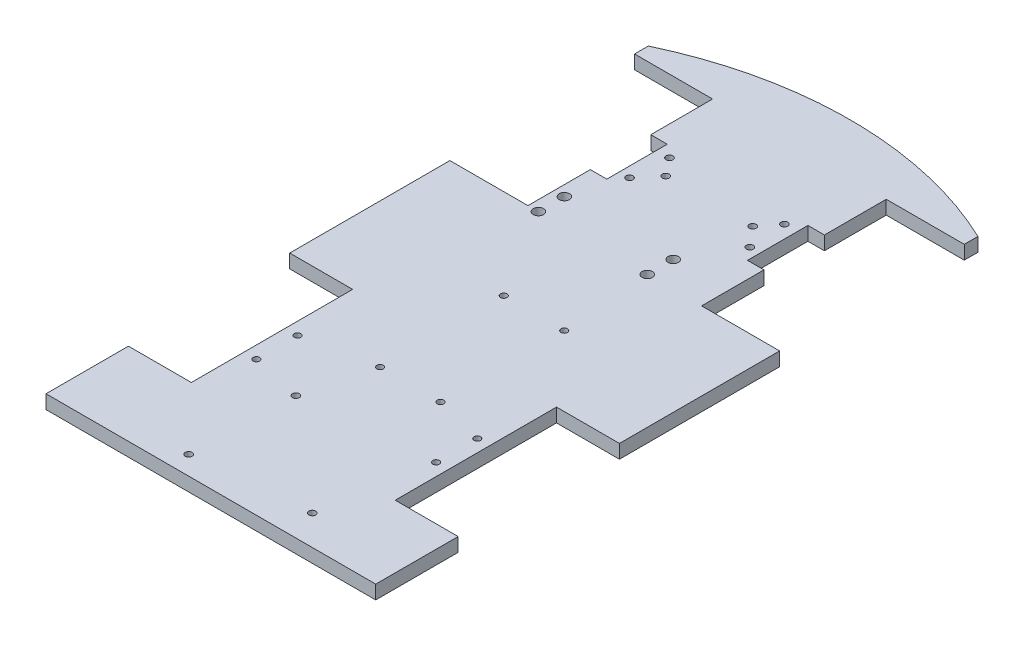
SolidWorks part; units mm, degrees
material "Oak"
ref_plane "Front Plane" through (0, 0, 0) normal (0, 0, 1) x (1, 0, 0)
ref_plane "Top Plane" through (0, 0, 0) normal (0, 1, 0) x (1, 0, 0)
ref_plane "Right Plane" through (0, 0, 0) normal (1, 0, 0) x (0, 0, -1)
sketch "Sketch1" plane through (0, 0, 0) normal (0, 1, 0) x (1, 0, 0)
  line L0 (50.292, 32.512) -> (76.2, 32.512) construction
  line L1 (0, 0) -> (0, -280.955) construction
  line L2 (0, 66.1738) -> (0, -229.362)
  line L3 (76.2, -229.362) -> (0, -229.362)
  line L7 (50.292, 32.512) -> (50.292, -32.512) construction
  line L8 (50.292, -32.512) -> (76.2, -32.512) construction
  line L9 (76.2, 32.512) -> (76.2, -32.512) construction
  line L10 (50.292, 32.512) -> (76.2, -32.512) construction
  line L11 (50.292, -32.512) -> (76.2, 32.512) construction
  line L18 (50.292, -119.888) -> (76.2, -119.888) construction
  line L19 (50.292, -119.888) -> (50.292, -184.912) construction
  line L20 (50.292, -184.912) -> (76.2, -184.912) construction
  line L21 (76.2, -119.888) -> (76.2, -184.912) construction
  line L22 (50.292, -119.888) -> (76.2, -184.912) construction
  line L23 (50.292, -184.912) -> (76.2, -119.888) construction
  line L25 (-76.2, 0) -> (76.2, 0) construction
  line L27 (-76.2, -152.4) -> (76.2, -152.4) construction
  line L28 (76.2, 0) -> (76.2, -152.4) construction
  line L33 (40.132, -42.672) -> (76.2, -42.672)
  line L34 (40.132, 42.672) -> (40.132, 14.097)
  line L35 (40.132, 42.672) -> (76.2, 42.672)
  line L36 (47.117, -191.262) -> (76.2, -191.262)
  line L37 (47.117, -116.713) -> (47.117, -191.262)
  line L38 (47.117, -116.713) -> (76.2, -116.713)
  line L43 (76.2, -42.672) -> (76.2, -116.713)
  line L45 (76.2, 42.672) -> (76.2, 49.022)
  line L47 (76.2, -191.262) -> (76.2, -229.362)
  line L55 (32.512, -13.843) -> (40.132, -13.843)
  line L56 (32.512, 14.097) -> (32.512, -13.843)
  line L57 (32.512, 14.097) -> (40.132, 14.097)
  line L58 (40.132, -13.843) -> (40.132, -42.672)
  arc A0 (0, 66.1738) -> (76.2, 49.022) centre (0, -111.6688) cw
  point P9 (63.246, 0)
  point P19 (63.246, -152.4)
  dimension "D7" = 3.175
  dimension "D8" = 6.35
  dimension "D12" = 7.62
  dimension "D16" = 6.35
  dimension "D1" = 152.4
  dimension "D2" = 152.4
  dimension "D3" = 126.492
  dimension "D4" = 25.908
  dimension "D6" = 3.175
  dimension "D9" = 10.16
  dimension "D10" = 10.16
  dimension "D5" = 65.024
  dimension "D11" = 10.16
  dimension "D13" = 27.94
  dimension "D14" = 28.575
  dimension "D15" = 38.1
extrude "Chassis" add sketch "Sketch1" along normal blind 6.35 contours L47 L36 L37 L38 L43 L33 L34 L55 L56 L57 L35 L45 region at (30.845, 0, 91.965)
mirror "Mirror1" about plane through (0, 6.35, 0) normal (1, 0, 0) of "Chassis"
sketch "Sketch2" plane through (0, 0, 0) normal (0, 1, 0) x (1, 0, 0)
  circle A0 centre (-26.5557, 9.17) radius 1.5875 construction
  circle A1 centre (-17.7031, -172.3599) radius 1.5875
  circle A2 centre (-17.7031, -172.3599) radius 1.5875
  circle A3 centre (-18.9731, -220.6199) radius 1.5875
  circle A4 centre (-18.9731, -220.6199) radius 1.5875
  circle A5 centre (33.0969, -215.5399) radius 1.5875
  circle A6 centre (33.0969, -215.5399) radius 1.5875
  circle A7 centre (-20.1056, 0.9994) radius 1.5875 construction
  circle A8 centre (-27.7865, -8.0406) radius 1.5875 construction
  circle A9 centre (26.5557, 9.17) radius 1.5875 construction
  circle A10 centre (20.1056, 0.9994) radius 1.5875 construction
  circle A11 centre (27.7865, -8.0406) radius 1.5875 construction
  circle A12 centre (15, -30.6528) radius 2.3812 construction
  circle A13 centre (15, -42.6528) radius 2.3813 construction
  circle A14 centre (-35.3, -30.6528) radius 2.3813 construction
  circle A15 centre (-35.3, -42.6528) radius 2.3813 construction
  circle A16 centre (18.288, -84.328) radius 1.5 construction
  circle A17 centre (-9.652, -84.328) radius 1.5 construction
  circle A18 centre (18.288, -141.478) radius 1.5 construction
  circle A19 centre (-9.652, -141.478) radius 1.5 construction
  circle A20 centre (-41.402, -147.875) radius 1.5 construction
  circle A21 centre (-41.402, -166.925) radius 1.5 construction
  circle A22 centre (41.402, -147.6053) radius 1.5 construction
  circle A23 centre (41.402, -166.6553) radius 1.5 construction
  circle A24 centre (-26.5557, 9.17) radius 1.5875
  circle A25 centre (-20.1056, 0.9994) radius 1.5875
  circle A26 centre (-27.7865, -8.0406) radius 1.5875
  circle A27 centre (26.5557, 9.17) radius 1.5875
  circle A28 centre (20.1056, 0.9994) radius 1.5875
  circle A29 centre (27.7865, -8.0406) radius 1.5875
  circle A30 centre (15, -30.6528) radius 2.3812
  circle A31 centre (15, -42.6528) radius 2.3813
  circle A32 centre (-35.3, -30.6528) radius 2.3813
  circle A33 centre (-35.3, -42.6528) radius 2.3812
  circle A34 centre (18.288, -84.328) radius 1.5
  circle A35 centre (-9.652, -84.328) radius 1.5
  circle A36 centre (18.288, -141.478) radius 1.5
  circle A37 centre (-9.652, -141.478) radius 1.5
  circle A38 centre (-41.402, -147.875) radius 1.5
  circle A39 centre (-41.402, -166.925) radius 1.5
  circle A40 centre (41.402, -147.6053) radius 1.5
  circle A41 centre (41.402, -166.6553) radius 1.5
  dimension "D1" = 0
  dimension "D2" = 0
  dimension "D3" = 0
extrude "Cut-Extrude1" cut sketch "Sketch2" along normal blind 17.78
